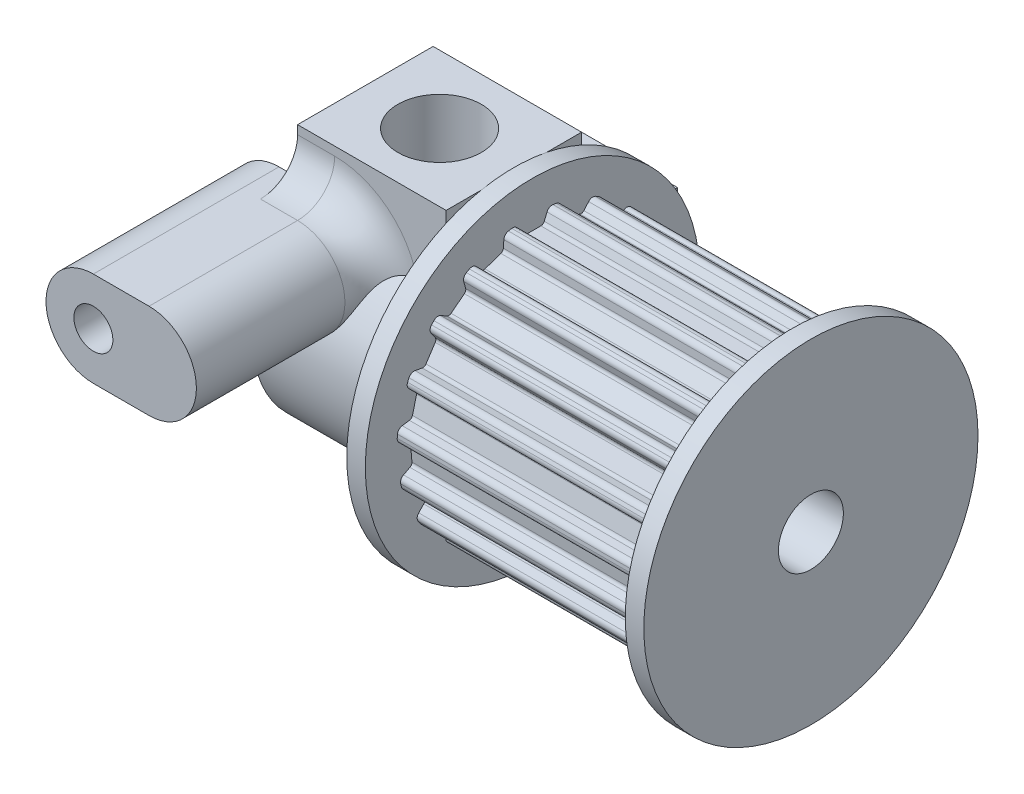
SolidWorks part; units mm, degrees
material "PLA Black"
ref_plane "Front" through (0, 0, 0) normal (0, 0, 1) x (1, 0, 0)
ref_plane "Top" through (0, 0, 0) normal (0, 1, 0) x (1, 0, 0)
ref_plane "Right" through (0, 0, 0) normal (1, 0, 0) x (0, 0, -1)
sketch "Sketch1" plane through (0, 0, 0) normal (1, 0, 0) x (0, 0, -1)
  line L0 (1.118, 1) -> (-1.118, 1) construction
  line L1 (-3.65, 4.8249) -> (3.65, 4.8249)
  line L2 (4.8249, 3.65) -> (4.8249, -3.65)
  line L3 (0, 0) -> (11.6334, 0) construction
  line L4 (0, 0) -> (0, 8.6732) construction
  arc A0 (-1.118, 1) -> (1.118, 1) centre (0, 0) ccw construction
  circle A1 centre (0, 0) radius 1.75
  arc A2 (4.8249, -3.65) -> (-3.65, 4.8249) centre (0, 0) cw
  arc A3 (4.8249, 3.65) -> (3.65, 4.8249) centre (0, 0) ccw
  dimension "D1" = 3
  dimension "D3" = 0.25
  dimension "D5" = 6.05
  dimension "D2" = 1
  dimension "D4" = 7.3
extrude "Boss-Extrude1" add sketch "Sketch1" along normal mid plane 8
sketch "Sketch2" plane through (0, 4.8249, 0) normal (0, 1, 0) x (1, 0, 0)
  circle A0 centre (0, 0) radius 2.25
  dimension "D1" = 4.5
extrude "Cut-Extrude1" cut sketch "Sketch2" against normal blind 5
sketch "Sketch7" plane through (4, 0, 0) normal (1, 0, 0) x (0, 0, -1)
  circle A0 centre (0, 0) radius 1.75 construction
  circle A1 centre (0, 0) radius 7.3
  circle A2 centre (0, 0) radius 1.75
  dimension "D1" = 14.6
extrude "Boss-Extrude5" add sketch "Sketch7" along normal blind 15
sketch "Sketch8" plane through (19, 0, 0) normal (1, 0, 0) x (0, 0, -1)
  line L0 (-0.4541, 6.5499) -> (0.4528, 6.5499)
  line L1 (0.6374, 6.6734) -> (0.7865, 7.0333)
  line L2 (-0.6389, 6.6734) -> (-0.788, 7.0333)
  line L6 (0, 9.2013) -> (0, 0) construction
  arc A0 (0.4528, 6.5499) -> (0.6374, 6.6734) centre (0.4526, 6.7499) ccw
  arc A1 (-0.4541, 6.5499) -> (-0.6389, 6.6734) centre (-0.4541, 6.7499) cw
  arc A2 (0.7865, 7.0333) -> (1.1093, 7.2152) centre (1.0638, 6.9187) cw
  arc A3 (-0.788, 7.0333) -> (-1.1108, 7.215) centre (-1.0652, 6.9185) ccw
  circle A4 centre (0, 0) radius 7.3 construction
  arc A5 (-1.1108, 7.215) -> (1.1093, 7.2152) centre (0, 0) cw
  point P3 (-0.0007, 6.5499)
  point P15 (0, 9.84)
extrude "Cut-Extrude3" cut sketch "Sketch8" against normal up to surface (15 mm away) up to face at (4, 0, -7.3)
pattern_circular "CirPattern1" count 19 over 360 about axis through (19, 0, 0) along (-1, 0, 0) of "Cut-Extrude3"
sketch "Sketch9" plane through (19, 0, 0) normal (1, 0, 0) x (0, 0, -1)
  circle A0 centre (0, 0) radius 9
  circle A1 centre (0, 0) radius 1.75 construction
  circle A2 centre (0, 0) radius 1.75
  dimension "D1" = 18
extrude "Boss-Extrude6" add sketch "Sketch9" along normal blind 1
sketch "Sketch10" plane through (4, 0, 0) normal (-1, 0, 0) x (0, 0, 1)
  circle A0 centre (0, 0) radius 9
  circle A1 centre (0, 0) radius 9 construction
  circle A2 centre (0, 0) radius 1.75 construction
  circle A3 centre (0, 0) radius 1.75
extrude "Boss-Extrude7" add sketch "Sketch10" against normal blind 1
sketch "Sketch3" plane through (0, 0, -4.8249) normal (0, 0, -1) x (-1, 0, 0)
  circle A0 centre (0, 0) radius 2.25
  dimension "D1" = 4.5
extrude "Cut-Extrude2" cut sketch "Sketch3" against normal blind 5
sketch "Sketch4" plane through (0, 4.8249, 0) normal (0, 1, 0) x (1, 0, 0)
  line L0 (4, 3.65) -> (-4, 3.65) construction
  line L2 (4, -3.65) -> (-4, -3.65) construction
  line L3 (-4, 3.65) -> (-4, -3.65) construction
  line L4 (4, 3.65) -> (-4, 3.65)
  line L5 (4, 3.65) -> (4, -3.65)
  line L6 (4, -3.65) -> (-4, -3.65)
  line L7 (-4, 3.65) -> (-4, -3.65)
  line L8 (4, 7.3) -> (4, -7.3) construction
  circle A0 centre (0, 0) radius 2.25 construction
  circle A1 centre (0, 0) radius 2.25
extrude "Boss-Extrude2" add sketch "Sketch4" along normal blind 4
sketch "Sketch5" plane through (0, 0, -4.8249) normal (0, 0, -1) x (-1, 0, 0)
  line L0 (-4, 3.65) -> (4, 3.65) construction
  line L1 (4, -3.65) -> (4, 3.65) construction
  line L2 (-4, -3.65) -> (4, -3.65) construction
  line L4 (-4, 3.65) -> (4, 3.65)
  line L5 (4, -3.65) -> (4, 3.65)
  line L6 (-4, -3.65) -> (4, -3.65)
  line L7 (-4, -3.65) -> (-4, 3.65)
  line L8 (-4, -7.3) -> (-4, 7.3) construction
  circle A0 centre (0, 0) radius 2.25 construction
  circle A1 centre (0, 0) radius 2.25
extrude "Boss-Extrude3" add sketch "Sketch5" along normal blind 4
ref_axis "Axis1" through (20, 0, 0) along (-1, 0, 0)
sketch "Sketch6" plane through (0, 0, 3.65) normal (0, 0, 1) x (1, 0, 0)
  line L0 (-4, 8.8249) -> (-4, 4.8249) construction
  line L2 (-2, 6.3555) -> (-5, 6.3555)
  line L3 (-5, 1.2545) -> (-2, 1.2545)
  line L6 (20, 0) -> (-4, 0) construction
  circle A0 centre (-5, 3.805) radius 1.0505
  arc A1 (-5, 6.3555) -> (-5, 1.2545) centre (-5, 3.805) ccw
  arc A2 (-2, 6.3555) -> (-2, 1.2545) centre (-2, 3.805) cw
  dimension "D1" = 2.101
  dimension "D2" = 3.805
  dimension "D3" = 1.5
  dimension "D4" = 1
  dimension "D5" = 3
extrude "Boss-Extrude4" add sketch "Sketch6" along normal blind 10
fillet "Fillet1" radius 2 2 edges at (-0.6029, 5.9388, 3.65) (-3, 6.3555, 3.65)
equation "\"knee_angle\"= 0"
equation "\"ankle_angle\" = 90"
equation "\"hip_angle\" = 0"
equation "\"spring_ankle_parallel_arm_diameter\"= 1.5"
equation "\"spring_ankle_parallel_arm_length\"= 13"
equation "\"spring_ankle_parallel_intern_diameter\"= 5.7"
equation "\"spring_ankle_parallel_angle\"= \"ankle_angle\""
equation "\"spring_ankle_parallel_turns\"= 3"
equation "\"spring_ankle_parallel_pitch\"= \"spring_ankle_parallel_arm_diameter\" * 1.01"
equation "\"spring_ankle_parallel_cutting_distance\"= (1-\"spring_ankle_parallel_angle\" / 360) * \"spring_ankle_parallel_pitch\""
equation "\"spring_ankle_serial_arm_diameter\"= 1.91"
equation "\"spring_ankle_serial_arm_length\"= 10"
equation "\"spring_ankle_serial_intern_diameter\"= 5.7"
equation "\"spring_ankle_serial_angle\"= \"90\""
equation "\"spring_ankle_serial_turns\"= 3"
equation "\"spring_ankle_serial_pitch\"= \"spring_ankle_serial_arm_diameter\" * 1.01"
equation "\"spring_ankle_serial_cutting_distance\"= (1-\"spring_ankle_serial_angle\" / 360) * \"spring_ankle_serial_pitch\""
equation "\"spring_knee_parallel_arm_diameter\"= 1.5"
equation "\"spring_knee_parallel_arm_length\"= 13"
equation "\"spring_knee_parallel_intern_diameter\"= 5.7"
equation "\"spring_knee_parallel_angle\"= -\"knee_angle\" + 90"
equation "\"spring_knee_parallel_turns\"= 3"
equation "\"spring_knee_parallel_pitch\"= \"spring_knee_parallel_arm_diameter\" * 1.01"
equation "\"spring_knee_parallel_cutting_distance\"= (1-(\"spring_knee_parallel_angle\") / 360) * \"spring_knee_parallel_pitch\""
equation "\"spring_knee_serial_arm_diameter\"= 1.91"
equation "\"spring_knee_serial_arm_length\"= 10"
equation "\"spring_knee_serial_intern_diameter\"= 5.7"
equation "\"spring_knee_serial_angle\"= \"90\""
equation "\"spring_knee_serial_turns\"= 3"
equation "\"spring_knee_serial_pitch\"= \"spring_knee_serial_arm_diameter\" * 1.01"
equation "\"spring_knee_serial_cutting_distance\"= (1-\"spring_knee_serial_angle\" / 360) * \"spring_knee_serial_pitch\""
equation "\"D2@Sketch6\" = ( \"spring_knee_serial_intern_diameter\" + \"spring_knee_serial_arm_diameter\" ) / 2"
equation "\"D1@Sketch6\"=\"spring_knee_serial_arm_diameter\"*1.1"
